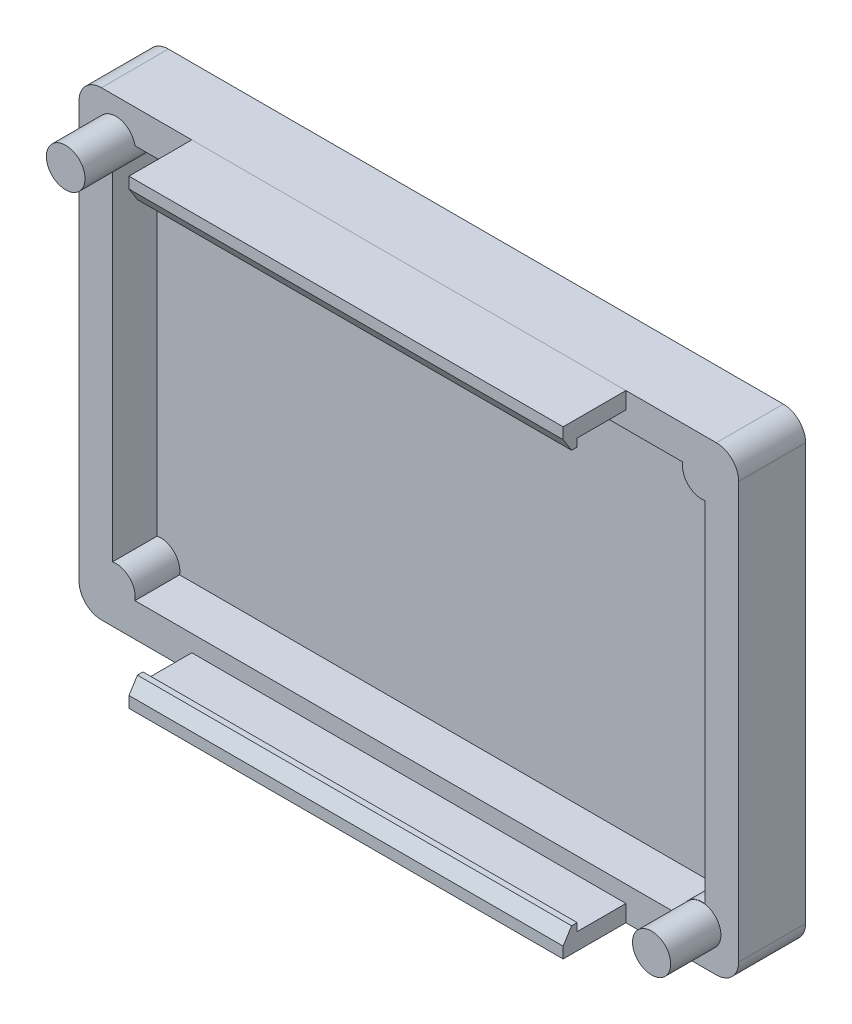
SolidWorks part; units mm, degrees
ref_plane "Płaszczyzna przednia" through (0, 0, 0) normal (0, 0, 1) x (1, 0, 0)
ref_plane "Płaszczyzna górna" through (0, 0, 0) normal (0, 1, 0) x (1, 0, 0)
ref_plane "Płaszczyzna prawa" through (0, 0, 0) normal (1, 0, 0) x (0, 0, -1)
sketch "Szkic1" plane through (0, 0, 48.1425) normal (0, 0, -1) x (-1, 0, 0)
  line L0 (25.6891, 14.5045) -> (25.6891, -16.1313) construction
  line L1 (23.6569, -18.1633) -> (-24.7789, -18.1633) construction
  line L2 (-26.8109, -16.1315) -> (-26.8109, 14.5047) construction
  line L3 (-24.7791, 16.5367) -> (23.6571, 16.5367) construction
  line L4 (25.6891, 14.5045) -> (25.6891, -16.1313)
  line L5 (23.6569, -18.1633) -> (-24.7789, -18.1633)
  line L6 (-26.8109, -16.1315) -> (-26.8109, 14.5047)
  line L7 (-24.7791, 16.5367) -> (23.6571, 16.5367)
  line L8 (-25.1053, 16.8367) -> (23.9833, 16.8367)
  line L9 (25.9891, 14.8307) -> (25.9891, -16.4575)
  line L10 (23.9831, -18.4633) -> (-25.1051, -18.4633)
  line L11 (-27.1109, -16.4577) -> (-27.1109, 14.8309)
  line L13 (-30.1109, -21.4633) -> (28.9891, -21.4633)
  line L14 (-30.1109, -21.4633) -> (-30.1109, 19.8367)
  line L15 (-30.1109, 19.8367) -> (28.9891, 19.8367)
  line L16 (28.9891, -21.4633) -> (28.9891, 19.8367)
  arc A0 (23.6571, 16.5367) -> (25.6891, 14.5045) centre (25.6891, 16.5365) ccw construction
  arc A1 (25.6891, -16.1313) -> (23.6569, -18.1633) centre (25.6891, -18.1635) ccw construction
  arc A2 (-24.7789, -18.1633) -> (-26.8109, -16.1315) centre (-26.8109, -18.1635) ccw construction
  arc A3 (-26.8109, 14.5047) -> (-24.7791, 16.5367) centre (-26.8109, 16.5365) ccw construction
  arc A4 (23.6571, 16.5367) -> (25.6891, 14.5045) centre (25.6891, 16.5365) ccw
  arc A5 (25.6891, -16.1313) -> (23.6569, -18.1633) centre (25.6891, -18.1635) ccw
  arc A6 (-24.7789, -18.1633) -> (-26.8109, -16.1315) centre (-26.8109, -18.1635) ccw
  arc A7 (-26.8109, 14.5047) -> (-24.7791, 16.5367) centre (-26.8109, 16.5365) ccw
  arc A8 (23.9833, 16.8367) -> (25.9891, 14.8307) centre (25.6891, 16.5365) ccw
  arc A9 (25.9891, -16.4575) -> (23.9831, -18.4633) centre (25.6891, -18.1635) ccw
  arc A10 (-25.1051, -18.4633) -> (-27.1109, -16.4577) centre (-26.8109, -18.1635) ccw
  arc A11 (-27.1109, 14.8309) -> (-25.1053, 16.8367) centre (-26.8109, 16.5365) ccw
  dimension "D2" = 3
  dimension "D3" = 3
  dimension "D4" = 3
  dimension "D5" = 3
  dimension "D1" = 0.3
extrude "Dodanie-wyciągnięcie1" add sketch "Szkic1" against normal blind 6 contours L13 L16 L15 L14 L11 A11 L8 A8 L9 A9 L10 A10 region at (29.3899, -0.8133, 48.1425)
sketch "Szkic2" plane through (0, 0, 48.1425) normal (0, 0, -1) x (-1, 0, 0)
  line L1 (-30.1109, 19.8367) -> (28.9891, 19.8367)
  line L2 (-30.1109, 19.8367) -> (-30.1109, -21.4633)
  line L3 (-30.1109, -21.4633) -> (28.9891, -21.4633)
  line L4 (28.9891, 19.8367) -> (28.9891, -21.4633)
extrude "Dodanie-wyciągnięcie2" add sketch "Szkic2" against normal blind 2
sketch "Szkic5" plane through (30.1109, 0, 0) normal (1, 0, 0) x (0, 0, -1)
  line L0 (-54.1425, 19.8367) -> (-59.7689, 19.8367)
  line L1 (-59.7689, 19.8367) -> (-59.7689, 18.8367)
  line L3 (-58.5127, 17.6367) -> (-58.5127, 18.3367)
  line L4 (-58.5127, 18.3367) -> (-54.1425, 18.3367)
  line L5 (-54.1425, -21.4633) -> (-54.1425, 19.8367) construction
  line L6 (-58.5127, 17.6367) -> (-59.0127, 17.6367)
  line L7 (-59.0127, 17.6367) -> (-59.7689, 18.8367)
  line L8 (-54.1425, 18.3367) -> (-54.1425, 19.8367)
  dimension "D1" = 1
  dimension "D2" = 0.7
  dimension "D3" = 5.6264
  dimension "D4" = 1.5
  dimension "D5" = 0.5
extrude "Dodanie-wyciągnięcie3" add sketch "Szkic5" against normal blind 49
extrude "Wytnij-wyciągnięcie2" cut sketch "Szkic5<2>" against normal blind 10.1
sketch "Szkic5<2>" plane through (30.1109, 0, 0) normal (1, 0, 0) x (0, 0, -1) same geometry as "Szkic5"
ref_point "Punkt1"
ref_axis "Oś1" through (30.1109, 19.8367, 54.1425) along (0, 0, -1)
ref_point "Punkt2"
ref_axis "Oś2" through (30.1109, -0.8133, 51.1425) along (0, 0, -1)
ref_plane "Płaszczyzna1" through (0, -0.8133, 0) normal (0, -1, 0) x (0, 0, -1)
mirror "Lustro3" about plane through (0, -0.8133, 0) normal (0, -1, 0) of bodies 105
sketch "Szkic10" plane through (0, 0, 54.1425) normal (0, 0, 1) x (1, 0, 0)
  circle A2 centre (26.8109, -18.1635) radius 1.7089
  circle A3 centre (-25.6891, 16.5365) radius 1.732
extrude "Dodanie-wyciągnięcie4" add sketch "Szkic10" along normal blind 4.5
fillet "Zaokrąglenie2" radius 2 4 edges at (-28.9891, 19.8367, 51.1425) (30.1109, 19.8367, 51.1425) (30.1109, -21.4633, 51.1425) (-28.9891, -21.4633, 51.1425)
